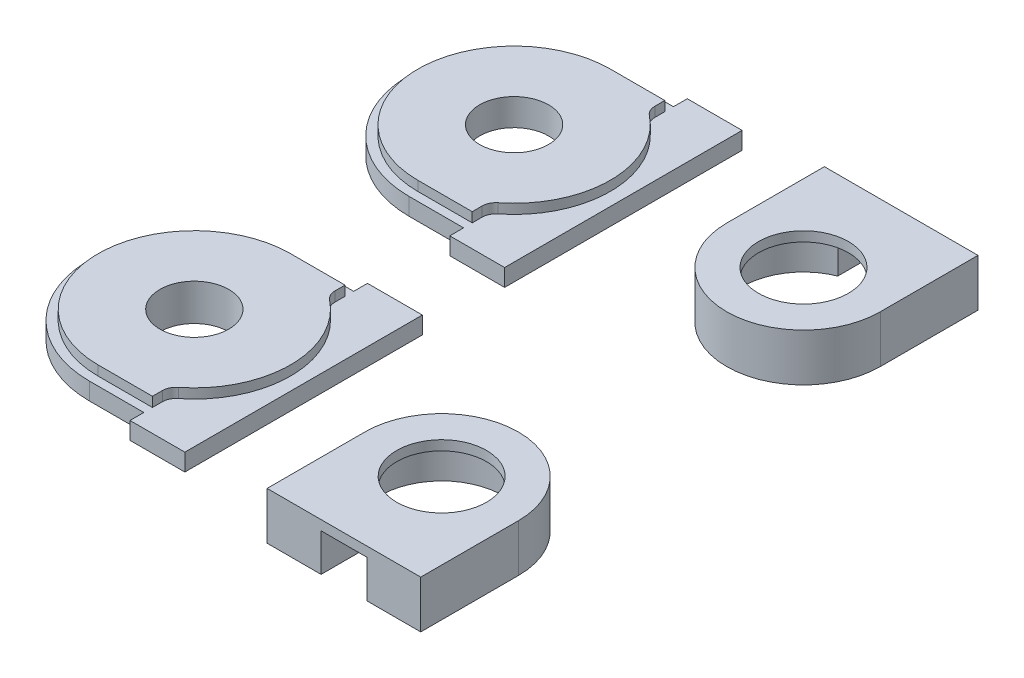
SolidWorks part; units mm, degrees
material "6061-T6 (SS)"
ref_plane "Front Plane" through (0, 0, 0) normal (0, 0, 1) x (1, 0, 0)
ref_plane "Top Plane" through (0, 0, 0) normal (0, 1, 0) x (1, 0, 0)
ref_plane "Right Plane" through (0, 0, 0) normal (1, 0, 0) x (0, 0, -1)
sketch "Sketch1" plane through (0, 0, 0) normal (0, 1, 0) x (1, 0, 0)
  line L0 (-13.2912, 20.8898) -> (-0.69, 20.8898)
  line L2 (-0.69, 24.0921) -> (-0.69, 20.8898)
  line L4 (12.01, 24.0921) -> (12.01, -26.9079)
  line L5 (-13.2912, -23.7056) -> (-0.69, -23.7056)
  line L6 (-0.69, -23.7056) -> (-0.69, -26.9079)
  line L13 (-0.69, -28.9079) -> (-0.69, -26.9079)
  line L15 (12.01, -28.9079) -> (12.01, -26.9079)
  line L16 (12.01, -28.9079) -> (-0.69, -28.9079)
  line L18 (12.01, 26.0921) -> (12.01, 24.0921)
  line L20 (-0.69, 26.0921) -> (-0.69, 24.0921)
  line L21 (-0.69, 26.0921) -> (12.01, 26.0921)
  arc A0 (-13.2912, 20.8898) -> (-13.2912, -23.7056) centre (-13.2912, -1.4079) ccw
extrude "Boss-Extrude1" add sketch "Sketch1" along normal blind 4
sketch "Sketch2" plane through (0, 4, 0) normal (0, 1, 0) x (1, 0, 0)
  line L0 (-0.69, 20.8898) -> (-0.69, 16.9877)
  line L1 (-0.69, -23.7056) -> (-0.69, -19.8035)
  line L2 (-0.69, -23.7056) -> (-13.2912, -23.7056)
  line L3 (-0.69, 20.8898) -> (-13.2912, 20.8898)
  arc A0 (-0.69, -19.8035) -> (-0.69, 16.9877) centre (-13.2912, -1.4079) ccw
  arc A1 (-13.2912, 20.8898) -> (-13.2912, -23.7056) centre (-13.2912, -1.4079) ccw
extrude "Boss-Extrude2" add sketch "Sketch2" along normal blind 2.25
sketch "Sketch3" plane through (0, 0, 0) normal (0, -1, 0) x (1, 0, 0)
  circle A0 centre (-13.2912, 1.4079) radius 7.975
  dimension "D1" = 15.95
extrude "Cut-Extrude1" cut sketch "Sketch3" against normal blind 9.25
sketch "Sketch5" plane through (0, 0, 0) normal (0, -1, 0) x (1, 0, 0)
  line L9 (-20.9332, 10.6275) -> (-24.2357, 16.3644)
  line L12 (-17.4546, 12.6358) -> (-20.7716, 18.3644)
  line L14 (-1.4858, 3.4163) -> (5.1338, 3.4079)
  line L17 (-1.4858, -0.6005) -> (5.1338, -0.5921)
  line L19 (-17.4546, -9.8201) -> (-20.7716, -15.5486)
  line L22 (-20.9332, -7.8117) -> (-24.2357, -13.5486)
  circle A2 centre (-13.2912, 1.4079) radius 11.975
  arc A3 (-1.4858, 3.4163) -> (-17.4546, 12.6358) centre (-13.2912, 1.4079) ccw
  circle A4 centre (-13.2912, 1.4079) radius 18.475
  circle A5 centre (-13.2912, 1.4079) radius 18.475
  circle A6 centre (-13.2912, 1.4079) radius 18.475
  circle A7 centre (-13.2912, 1.4079) radius 18.475
  arc A8 (-20.9332, 10.6275) -> (-20.9332, -7.8117) centre (-13.2912, 1.4079) ccw
  arc A9 (-17.4546, -9.8201) -> (-1.4858, -0.6005) centre (-13.2912, 1.4079) ccw
  point P14 (-13.2912, 1.4079)
  dimension "D1" = 4
  dimension "D2" = 10.5
  dimension "D3" = 3
extrude "Cut-Extrude3" cut sketch "Sketch5" against normal blind 3.1 contours A8 L9 A4 L22 | L14 A4 L12 A3 | A9 L19 A4 L17 region at (-26.6974, 0, 1.4079) region at (-6.5881, 0, 13.018) region at (-6.5881, 0, -10.2022)
fillet "Fillet1" radius 3.175 12 edges at (5.0752, 1.55, 3.408) (-1.4858, 1.55, 3.4163) (5.0752, 1.55, -0.5922) (-24.2065, 1.55, 16.3136) (-20.7423, 1.55, 18.3137) (-1.4858, 1.55, -0.6005) (-20.7423, 1.55, -15.4979) (-20.9332, 1.55, 10.6275) (-20.9332, 1.55, -7.8117) (-24.2065, 1.55, -13.4979) (-17.4546, 1.55, -9.8201) (-17.4546, 1.55, 12.6358)
sketch "Sketch6" plane through (0, 0, 0) normal (0, -1, 0) x (1, 0, 0)
  line L2 (-0.69, -22.8898) -> (-13.2912, -22.8898)
  line L3 (-13.2912, 25.7056) -> (-0.69, 25.7056)
  line L4 (-0.69, -20.8898) -> (-13.2912, -20.8898)
  line L5 (-13.2912, 23.7056) -> (-0.69, 23.7056)
  line L6 (-0.69, -20.8898) -> (-13.2912, -20.8898)
  line L7 (-13.2912, 23.7056) -> (-0.69, 23.7056)
  line L8 (-0.69, 25.7056) -> (-0.69, 23.7056)
  line L9 (-0.69, -20.8898) -> (-0.69, -22.8898)
  arc A1 (-13.2912, 25.7056) -> (-13.2912, -22.8898) centre (-13.2912, 1.4079) ccw
  arc A2 (-13.2912, 23.7056) -> (-13.2912, -20.8898) centre (-13.2912, 1.4079) ccw
  arc A3 (-13.2912, 23.7056) -> (-13.2912, -20.8898) centre (-13.2912, 1.4079) ccw
  dimension "D1" = 0
  dimension "D2" = 2
extrude "Boss-Extrude3" add sketch "Sketch6" against normal blind 4
ref_axis "Axis2" through (-13.2912, 6.25, 1.4079) along (0, -1, 0)
fillet "Fillet3" radius 3.175 2 edges at (-0.69, 5.125, -16.9877) (-0.69, 5.125, 19.8035)
ref_plane "Plane1" through (0, 0, 38.4329) normal (0, 0, 1) x (1, 0, 0)
sketch "Sketch7" plane through (12.01, 0, 0) normal (1, 0, 0) x (0, 0, -1)
  line L0 (-20.8141, 0) -> (-38.4329, 0)
  line L1 (-28.9079, 0) -> (26.0921, 0) construction
  line L2 (-38.4329, 51.2246) -> (-38.4329, -51.2246) construction
  line L3 (-38.4329, 0) -> (-38.4329, -1.7696)
  line L4 (-38.4329, -1.7696) -> (-20.8141, -1.7696)
  line L5 (-20.8141, -1.7696) -> (-20.8141, 0)
extrude "Boss-Extrude4" add sketch "Sketch7" against normal blind 10
mirror "Mirror2" about plane through (0, 0, 38.4329) normal (0, 0, 1) of bodies 108
sketch "Sketch8" plane through (12.01, 0, 0) normal (1, 0, 0) x (0, 0, -1)
  line L1 (-20.8141, -1.7696) -> (-56.0517, -1.7696)
  line L2 (-20.8141, -1.7696) -> (-20.8141, 0)
  line L3 (-20.8141, 0) -> (-56.0517, 0)
  line L4 (-56.0517, -1.7696) -> (-56.0517, 0)
extrude "Cut-Extrude4" cut sketch "Sketch8" against normal blind 10
sketch "Sketch9" plane through (0, 0, 0) normal (0, -1, 0) x (1, 0, 0)
  circle A0 centre (-13.2912, 75.4579) radius 11.975
  circle A1 centre (-13.2912, 75.4579) radius 7.975
extrude "Boss-Extrude5" add sketch "Sketch9" along normal blind 2.25
sketch "Sketch10" plane through (0, 6.25, 0) normal (0, 1, 0) x (1, 0, 0)
  line L0 (12.01, -28.9079) -> (12.01, -47.9579) construction
  line L1 (12.01, -38.4329) -> (55.3994, -38.4329) construction
  line L2 (31.06, -102.9579) -> (43.5595, -102.9579)
  line L6 (12.01, -102.9579) -> (31.06, -102.9579) construction
  line L7 (31.06, -80.3298) -> (31.06, -102.9579)
  line L8 (66.635, -80.3298) -> (66.635, -102.9579)
  line L10 (43.5595, -102.9579) -> (43.5595, -93.5623)
  line L12 (54.1355, -93.5623) -> (54.1355, -102.9579)
  line L13 (54.1355, -102.9579) -> (66.635, -102.9579)
  line L14 (54.1355, 26.0921) -> (66.635, 26.0921)
  line L15 (54.1355, 16.6965) -> (54.1355, 26.0921)
  line L16 (43.5595, 26.0921) -> (43.5595, 16.6965)
  line L17 (66.635, 3.464) -> (66.635, 26.0921)
  line L18 (31.06, 3.464) -> (31.06, 26.0921)
  line L19 (31.06, 26.0921) -> (43.5595, 26.0921)
  arc A2 (54.1355, -93.5623) -> (43.5595, -93.5623) centre (48.8475, -80.3298) ccw
  arc A3 (66.635, -80.3298) -> (31.06, -80.3298) centre (48.8475, -80.3298) ccw
  arc A4 (66.635, 3.464) -> (31.06, 3.464) centre (48.8475, 3.464) cw
  arc A5 (54.1355, 16.6965) -> (43.5595, 16.6965) centre (48.8475, 3.464) cw
  point P9 (0, 0)
  point P10 (0, 0)
extrude "Boss-Extrude6" add sketch "Sketch10" against normal blind 11 separate body
sketch "Sketch11" plane through (0, 6.25, 0) normal (0, 1, 0) x (1, 0, 0)
  line L3 (43.5595, -102.9579) -> (54.1355, -102.9579)
  line L4 (12.01, -28.9079) -> (12.01, -47.9579) construction
  line L5 (43.5595, -102.9579) -> (43.5595, -93.5623)
  line L6 (54.1355, -93.5623) -> (54.1355, -102.9579)
  line L7 (43.5595, -102.9579) -> (43.5595, -93.5623)
  line L8 (54.1355, -93.5623) -> (54.1355, -102.9579)
  line L9 (12.01, -38.4329) -> (77.2075, -38.4329) construction
  line L10 (54.1355, 16.6965) -> (54.1355, 26.0921)
  line L11 (43.5595, 26.0921) -> (43.5595, 16.6965)
  line L12 (43.5595, 26.0921) -> (54.1355, 26.0921)
  circle A3 centre (48.8475, -80.3298) radius 10.4013
  arc A4 (54.1355, -93.5623) -> (43.5595, -93.5623) centre (48.8475, -80.3298) ccw
  arc A5 (54.1355, -93.5623) -> (43.5595, -93.5623) centre (48.8475, -80.3298) ccw
  arc A6 (54.1355, 16.6965) -> (43.5595, 16.6965) centre (48.8475, 3.464) cw
  circle A7 centre (48.8475, 3.464) radius 10.4013
  dimension "D2" = 20.8026
  dimension "D1" = 0
extrude "Boss-Extrude9" add sketch "Sketch11" against normal blind 2.25
